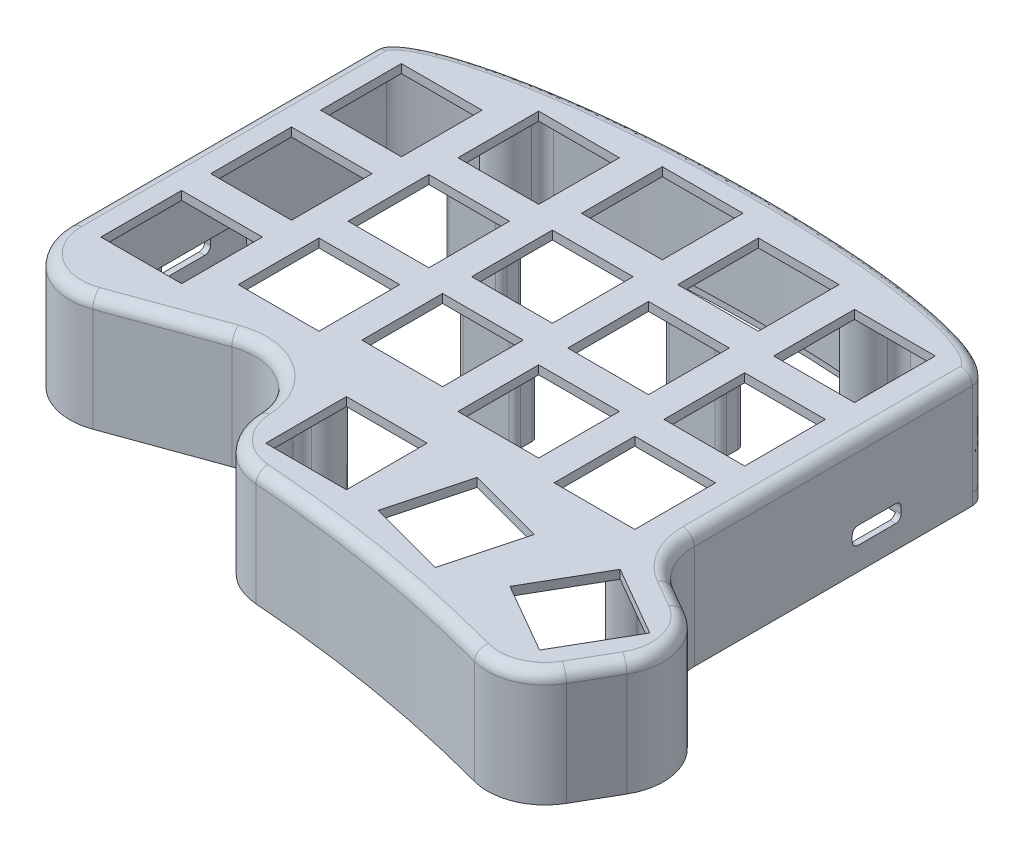
SolidWorks part; units mm, degrees
ref_plane "Front Plane" through (0, 0, 0) normal (0, 0, 1) x (1, 0, 0)
ref_plane "Top Plane" through (0, 0, 0) normal (0, 1, 0) x (1, 0, 0)
ref_plane "Right Plane" through (0, 0, 0) normal (1, 0, 0) x (0, 0, -1)
sketch "Sketch2" plane through (0, 0, 0) normal (0, 1, 0) x (1, 0, 0)
  line L0 (-52.3875, 73.6763) -> (-52.3875, 21.5763) construction
  line L1 (-60.1375, 66.6763) -> (-44.6375, 66.6763) construction
  line L2 (-52.1341, 56.3684) -> (-52.1341, 68.3684) construction
  line L4 (-102.7306, 67.1244) -> (-102.7306, 14.2787)
  line L5 (-1.5375, 69.6125) -> (-1.5375, 21.3832)
  line L13 (3.4635, 12.7224) -> (8.1059, 10.0427)
  line L14 (11.7677, -3.6171) -> (7.9274, -10.2704)
  line L15 (-89.3298, 4.8748) -> (-71.6235, 11.2781)
  line L24 (-90.4875, 66.5312) -> (-90.4875, 52.5312) construction
  line L26 (-71.4375, 71.2937) -> (-71.4375, 57.2937) construction
  line L28 (-52.3875, 73.6763) -> (-52.3875, 59.6763) construction
  line L30 (-33.3375, 71.2938) -> (-33.3375, 57.2938) construction
  line L32 (-14.2875, 68.9138) -> (-14.2875, 54.9138) construction
  line L34 (-90.4875, 47.4812) -> (-90.4875, 33.4812) construction
  line L36 (-71.4375, 52.2437) -> (-71.4375, 38.2437) construction
  line L38 (-52.3875, 54.6263) -> (-52.3875, 40.6263) construction
  line L40 (-33.3375, 52.2438) -> (-33.3375, 38.2438) construction
  line L42 (-14.2875, 49.8638) -> (-14.2875, 35.8638) construction
  line L44 (-14.2875, 30.8138) -> (-14.2875, 16.8138) construction
  line L46 (-33.3375, 33.1938) -> (-33.3375, 19.1937) construction
  line L48 (-71.4375, 33.1937) -> (-71.4375, 19.1937) construction
  line L51 (-90.4875, 28.4312) -> (-90.4875, 14.4312) construction
  line L52 (-52.3875, 35.5763) -> (-52.3875, 21.5763) construction
  line L54 (-45.2425, 11.7638) -> (-45.2425, -2.2362) construction
  line L56 (-83.4875, 52.5312) -> (-97.4875, 52.5312)
  line L57 (-83.4875, 52.5312) -> (-83.4875, 66.5312)
  line L58 (-83.4875, 66.5312) -> (-97.4875, 66.5312)
  line L59 (-97.4875, 52.5312) -> (-97.4875, 66.5312)
  line L60 (-83.4875, 52.5312) -> (-97.4875, 66.5312) construction
  line L61 (-83.4875, 66.5312) -> (-97.4875, 52.5312) construction
  line L63 (-64.4375, 57.2937) -> (-78.4375, 57.2937)
  line L64 (-64.4375, 57.2937) -> (-64.4375, 71.2937)
  line L65 (-64.4375, 71.2937) -> (-78.4375, 71.2937)
  line L66 (-78.4375, 57.2937) -> (-78.4375, 71.2937)
  line L67 (-64.4375, 57.2937) -> (-78.4375, 71.2937) construction
  line L68 (-64.4375, 71.2937) -> (-78.4375, 57.2937) construction
  line L71 (-45.3875, 59.6763) -> (-59.3875, 59.6763)
  line L72 (-45.3875, 59.6763) -> (-45.3875, 73.6763)
  line L73 (-45.3875, 73.6763) -> (-59.3875, 73.6763)
  line L74 (-59.3875, 59.6763) -> (-59.3875, 73.6763)
  line L75 (-45.3875, 59.6763) -> (-59.3875, 73.6763) construction
  line L76 (-45.3875, 73.6763) -> (-59.3875, 59.6763) construction
  line L78 (-26.3375, 57.2937) -> (-40.3375, 57.2937)
  line L79 (-26.3375, 57.2937) -> (-26.3375, 71.2937)
  line L80 (-26.3375, 71.2937) -> (-40.3375, 71.2937)
  line L81 (-40.3375, 57.2937) -> (-40.3375, 71.2937)
  line L82 (-26.3375, 57.2937) -> (-40.3375, 71.2937) construction
  line L83 (-26.3375, 71.2937) -> (-40.3375, 57.2937) construction
  line L85 (-7.2875, 54.9138) -> (-21.2875, 54.9138)
  line L86 (-7.2875, 54.9138) -> (-7.2875, 68.9138)
  line L87 (-7.2875, 68.9138) -> (-21.2875, 68.9138)
  line L88 (-21.2875, 54.9138) -> (-21.2875, 68.9138)
  line L89 (-7.2875, 54.9138) -> (-21.2875, 68.9138) construction
  line L90 (-7.2875, 68.9138) -> (-21.2875, 54.9138) construction
  line L92 (-7.2875, 35.8638) -> (-21.2875, 35.8638)
  line L93 (-7.2875, 35.8638) -> (-7.2875, 49.8638)
  line L94 (-7.2875, 49.8638) -> (-21.2875, 49.8638)
  line L95 (-21.2875, 35.8638) -> (-21.2875, 49.8638)
  line L96 (-7.2875, 35.8638) -> (-21.2875, 49.8638) construction
  line L97 (-7.2875, 49.8638) -> (-21.2875, 35.8638) construction
  line L99 (-26.3375, 38.2437) -> (-40.3375, 38.2437)
  line L100 (-26.3375, 38.2437) -> (-26.3375, 52.2437)
  line L101 (-26.3375, 52.2437) -> (-40.3375, 52.2437)
  line L102 (-40.3375, 38.2437) -> (-40.3375, 52.2437)
  line L103 (-26.3375, 38.2437) -> (-40.3375, 52.2437) construction
  line L104 (-26.3375, 52.2437) -> (-40.3375, 38.2437) construction
  line L106 (-45.3875, 40.6263) -> (-59.3875, 40.6263)
  line L107 (-45.3875, 40.6263) -> (-45.3875, 54.6263)
  line L108 (-45.3875, 54.6263) -> (-59.3875, 54.6263)
  line L109 (-59.3875, 40.6263) -> (-59.3875, 54.6263)
  line L110 (-45.3875, 40.6263) -> (-59.3875, 54.6263) construction
  line L111 (-45.3875, 54.6263) -> (-59.3875, 40.6263) construction
  line L113 (-64.4375, 38.2437) -> (-78.4375, 38.2437)
  line L114 (-64.4375, 38.2437) -> (-64.4375, 52.2437)
  line L115 (-64.4375, 52.2437) -> (-78.4375, 52.2437)
  line L116 (-78.4375, 38.2437) -> (-78.4375, 52.2437)
  line L117 (-64.4375, 38.2437) -> (-78.4375, 52.2437) construction
  line L118 (-64.4375, 52.2437) -> (-78.4375, 38.2437) construction
  line L120 (-83.4875, 33.4812) -> (-97.4875, 33.4812)
  line L121 (-83.4875, 33.4812) -> (-83.4875, 47.4812)
  line L122 (-83.4875, 47.4812) -> (-97.4875, 47.4812)
  line L123 (-97.4875, 33.4812) -> (-97.4875, 47.4812)
  line L124 (-83.4875, 33.4812) -> (-97.4875, 47.4812) construction
  line L125 (-83.4875, 47.4812) -> (-97.4875, 33.4812) construction
  line L127 (-83.4875, 14.4312) -> (-97.4875, 14.4312)
  line L128 (-83.4875, 14.4312) -> (-83.4875, 28.4312)
  line L129 (-83.4875, 28.4312) -> (-97.4875, 28.4312)
  line L130 (-97.4875, 14.4312) -> (-97.4875, 28.4312)
  line L131 (-83.4875, 14.4312) -> (-97.4875, 28.4312) construction
  line L132 (-83.4875, 28.4312) -> (-97.4875, 14.4312) construction
  line L134 (-64.4375, 19.1937) -> (-78.4375, 19.1937)
  line L135 (-64.4375, 19.1937) -> (-64.4375, 33.1937)
  line L136 (-64.4375, 33.1937) -> (-78.4375, 33.1937)
  line L137 (-78.4375, 19.1937) -> (-78.4375, 33.1937)
  line L138 (-64.4375, 19.1937) -> (-78.4375, 33.1937) construction
  line L139 (-64.4375, 33.1937) -> (-78.4375, 19.1937) construction
  line L141 (-26.3375, 19.1937) -> (-40.3375, 19.1937)
  line L142 (-26.3375, 19.1937) -> (-26.3375, 33.1937)
  line L143 (-26.3375, 33.1937) -> (-40.3375, 33.1937)
  line L144 (-40.3375, 19.1937) -> (-40.3375, 33.1937)
  line L145 (-26.3375, 19.1937) -> (-40.3375, 33.1937) construction
  line L146 (-26.3375, 33.1937) -> (-40.3375, 19.1937) construction
  line L148 (-7.2875, 16.8138) -> (-21.2875, 16.8138)
  line L149 (-7.2875, 16.8138) -> (-7.2875, 30.8138)
  line L150 (-7.2875, 30.8138) -> (-21.2875, 30.8138)
  line L151 (-21.2875, 16.8138) -> (-21.2875, 30.8138)
  line L152 (-7.2875, 16.8138) -> (-21.2875, 30.8138) construction
  line L153 (-7.2875, 30.8138) -> (-21.2875, 16.8138) construction
  line L155 (-38.2425, -2.2362) -> (-52.2425, -2.2362)
  line L156 (-38.2425, -2.2362) -> (-38.2425, 11.7638)
  line L157 (-38.2425, 11.7638) -> (-52.2425, 11.7638)
  line L158 (-52.2425, -2.2362) -> (-52.2425, 11.7638)
  line L159 (-38.2425, -2.2362) -> (-52.2425, 11.7638) construction
  line L160 (-38.2425, 11.7638) -> (-52.2425, -2.2362) construction
  line L161 (-60.1375, 28.5763) -> (-44.6375, 28.5763) construction
  line L163 (-21.9997, 9.1424) -> (-25.6253, -4.3799) construction
  line L166 (-45.3875, 21.5763) -> (-59.3875, 21.5763)
  line L167 (-45.3875, 21.5763) -> (-45.3875, 35.5763)
  line L168 (-45.3875, 35.5763) -> (-59.3875, 35.5763)
  line L169 (-59.3875, 21.5763) -> (-59.3875, 35.5763)
  line L170 (-45.3875, 21.5763) -> (-59.3875, 35.5763) construction
  line L171 (-45.3875, 35.5763) -> (-59.3875, 21.5763) construction
  line L173 (-18.8641, -6.1927) -> (-32.3865, -2.5672)
  line L174 (-18.8641, -6.1927) -> (-15.2385, 7.3297)
  line L175 (-15.2385, 7.3297) -> (-28.7609, 10.9552)
  line L176 (-32.3865, -2.5672) -> (-28.7609, 10.9552)
  line L177 (-18.8641, -6.1927) -> (-28.7609, 10.9552) construction
  line L178 (-15.2385, 7.3297) -> (-32.3865, -2.5672) construction
  line L180 (2.5633, -9.5619) -> (-9.5619, -2.5633)
  line L181 (2.5633, -9.5619) -> (9.5619, 2.5633)
  line L182 (9.5619, 2.5633) -> (-2.5633, 9.5619)
  line L183 (-9.5619, -2.5633) -> (-2.5633, 9.5619)
  line L184 (2.5633, -9.5619) -> (-2.5633, 9.5619) construction
  line L185 (9.5619, 2.5633) -> (-9.5619, -2.5633) construction
  arc A0 (-71.6235, 11.2781) -> (-58.2326, 2.3189) centre (-68.2227, 1.8741) cw
  arc A1 (-102.7306, 14.2787) -> (-89.3298, 4.8748) centre (-92.7306, 14.2787) ccw
  arc A2 (-1.5375, 21.3832) -> (3.4635, 12.7224) centre (8.4625, 21.3832) ccw
  arc A3 (8.1059, 10.0427) -> (11.7677, -3.6171) centre (3.1069, 1.3819) cw
  arc A4 (-48.9528, -7.211) -> (-3.3427, -14.9249) centre (-66.0135, -246.7815) cw
  arc A5 (7.9274, -10.2704) -> (-3.3427, -14.9249) centre (-0.7334, -5.2713) cw
  arc A6 (-58.2326, 2.3189) -> (-48.9528, -7.211) centre (-48.2425, 2.7638) ccw
  ellipse E0 centre (-52.1341, 56.3684) end of major axis (-1.5375, 57.6125) minor radius 10.3109 construction
  ellipse E1 centre (-52.1341, 68.3684) end of major axis (-1.5375, 69.6125) minor radius 10.3109 (-52.3875, 58.0487) -> (-52.1341, 58.0545) ccw
  ellipse E2 centre (-52.1341, 68.3684) end of major axis (-1.5375, 69.6125) minor radius 10.3109 (-1.5375, 69.6125) -> (-102.7306, 67.1244) ccw
  point P1 (-98.2375, 59.5312)
  point P3 (-6.5375, 61.9138)
  point P34 (-20.1589, -11.0222)
  point P39 (4.0192, -17.0414)
  point P86 (-71.4375, 64.2937)
  point P88 (-90.4875, 59.5312)
  point P96 (-52.3875, 66.6763)
  point P101 (-33.3375, 64.2938)
  point P106 (-14.2875, 61.9138)
  point P111 (-14.2875, 42.8638)
  point P116 (-33.3375, 45.2438)
  point P121 (-52.3875, 47.6263)
  point P126 (-71.4375, 45.2437)
  point P131 (-90.4875, 40.4812)
  point P136 (-90.4875, 21.4312)
  point P141 (-71.4375, 26.1937)
  point P146 (-33.3375, 26.1938)
  point P151 (-14.2875, 23.8138)
  point P156 (-45.2425, 4.7638)
  point P165 (-52.3875, 28.5763)
  point P170 (-23.8125, 2.3812)
  point P175 (0, 0)
  line B0 (3.8742, 6.7121) -> (-3.8742, -6.7121) construction
  line B1 (-6.0626, 3.4993) -> (6.0626, -3.4993) construction
  line B2 (9.0422, 2.8632) -> (9.4172, 3.5128)
  line B3 (9.4172, 3.5128) -> (-1.6687, 9.9115)
  line B4 (-1.6687, 9.9115) -> (-2.0436, 9.2619)
  line B5 (-2.0436, 9.2619) -> (-2.5633, 9.5619)
  line B6 (-2.5633, 9.5619) -> (-9.5619, -2.5633)
  line B7 (-9.5619, -2.5633) -> (-9.0422, -2.8632)
  line B8 (-9.0422, -2.8632) -> (-9.4172, -3.5128)
  line B9 (-9.4172, -3.5128) -> (1.6687, -9.9115)
  line B10 (1.6687, -9.9115) -> (2.0436, -9.2619)
  line B11 (2.0436, -9.2619) -> (2.5633, -9.5619)
  line B12 (2.5633, -9.5619) -> (9.5619, 2.5633)
  line B13 (9.5619, 2.5633) -> (9.0422, 2.8632)
  line B14 (-83.4875, 53.1312) -> (-82.7375, 53.1312)
  line B15 (-82.7375, 53.1312) -> (-82.7375, 65.9312)
  line B16 (-82.7375, 65.9312) -> (-83.4875, 65.9312)
  line B17 (-83.4875, 65.9312) -> (-83.4875, 66.5312)
  line B18 (-83.4875, 66.5312) -> (-97.4875, 66.5312)
  line B19 (-97.4875, 66.5312) -> (-97.4875, 65.9312)
  line B20 (-97.4875, 65.9312) -> (-98.2375, 65.9312)
  line B21 (-98.2375, 65.9312) -> (-98.2375, 53.1312)
  line B22 (-98.2375, 53.1312) -> (-97.4875, 53.1312)
  line B23 (-97.4875, 53.1312) -> (-97.4875, 52.5312)
  line B24 (-97.4875, 52.5312) -> (-83.4875, 52.5312)
  line B25 (-83.4875, 52.5312) -> (-83.4875, 53.1312)
  line B26 (-7.2875, 55.5138) -> (-6.5375, 55.5138)
  line B27 (-6.5375, 55.5138) -> (-6.5375, 68.3138)
  line B28 (-6.5375, 68.3138) -> (-7.2875, 68.3138)
  line B29 (-7.2875, 68.3138) -> (-7.2875, 68.9138)
  line B30 (-7.2875, 68.9138) -> (-21.2875, 68.9138)
  line B31 (-21.2875, 68.9138) -> (-21.2875, 68.3138)
  line B32 (-21.2875, 68.3138) -> (-22.0375, 68.3138)
  line B33 (-22.0375, 68.3138) -> (-22.0375, 55.5138)
  line B34 (-22.0375, 55.5138) -> (-21.2875, 55.5138)
  line B35 (-21.2875, 55.5138) -> (-21.2875, 54.9138)
  line B36 (-21.2875, 54.9138) -> (-7.2875, 54.9138)
  line B37 (-7.2875, 54.9138) -> (-7.2875, 55.5138)
  line B38 (-26.3375, 57.8938) -> (-25.5875, 57.8938)
  line B39 (-25.5875, 57.8938) -> (-25.5875, 70.6938)
  line B40 (-25.5875, 70.6938) -> (-26.3375, 70.6938)
  line B41 (-26.3375, 70.6938) -> (-26.3375, 71.2938)
  line B42 (-26.3375, 71.2938) -> (-40.3375, 71.2938)
  line B43 (-40.3375, 71.2938) -> (-40.3375, 70.6938)
  line B44 (-40.3375, 70.6938) -> (-41.0875, 70.6938)
  line B45 (-41.0875, 70.6938) -> (-41.0875, 57.8938)
  line B46 (-41.0875, 57.8938) -> (-40.3375, 57.8938)
  line B47 (-40.3375, 57.8938) -> (-40.3375, 57.2938)
  line B48 (-40.3375, 57.2938) -> (-26.3375, 57.2938)
  line B49 (-26.3375, 57.2938) -> (-26.3375, 57.8938)
  line B50 (-64.4375, 57.8937) -> (-63.6875, 57.8937)
  line B51 (-63.6875, 57.8937) -> (-63.6875, 70.6937)
  line B52 (-63.6875, 70.6937) -> (-64.4375, 70.6937)
  line B53 (-64.4375, 70.6937) -> (-64.4375, 71.2937)
  line B54 (-64.4375, 71.2937) -> (-78.4375, 71.2937)
  line B55 (-78.4375, 71.2937) -> (-78.4375, 70.6937)
  line B56 (-78.4375, 70.6937) -> (-79.1875, 70.6937)
  line B57 (-79.1875, 70.6937) -> (-79.1875, 57.8937)
  line B58 (-79.1875, 57.8937) -> (-78.4375, 57.8937)
  line B59 (-78.4375, 57.8937) -> (-78.4375, 57.2937)
  line B60 (-78.4375, 57.2937) -> (-64.4375, 57.2937)
  line B61 (-64.4375, 57.2937) -> (-64.4375, 57.8937)
  line B62 (-83.4875, 15.0312) -> (-82.7375, 15.0312)
  line B63 (-82.7375, 15.0312) -> (-82.7375, 27.8312)
  line B64 (-82.7375, 27.8312) -> (-83.4875, 27.8312)
  line B65 (-83.4875, 27.8312) -> (-83.4875, 28.4312)
  line B66 (-83.4875, 28.4312) -> (-97.4875, 28.4312)
  line B67 (-97.4875, 28.4312) -> (-97.4875, 27.8312)
  line B68 (-97.4875, 27.8312) -> (-98.2375, 27.8312)
  line B69 (-98.2375, 27.8312) -> (-98.2375, 15.0312)
  line B70 (-98.2375, 15.0312) -> (-97.4875, 15.0312)
  line B71 (-97.4875, 15.0312) -> (-97.4875, 14.4312)
  line B72 (-97.4875, 14.4312) -> (-83.4875, 14.4312)
  line B73 (-83.4875, 14.4312) -> (-83.4875, 15.0312)
  line B74 (-83.4875, 34.0812) -> (-82.7375, 34.0812)
  line B75 (-82.7375, 34.0812) -> (-82.7375, 46.8812)
  line B76 (-82.7375, 46.8812) -> (-83.4875, 46.8812)
  line B77 (-83.4875, 46.8812) -> (-83.4875, 47.4812)
  line B78 (-83.4875, 47.4812) -> (-97.4875, 47.4812)
  line B79 (-97.4875, 47.4812) -> (-97.4875, 46.8812)
  line B80 (-97.4875, 46.8812) -> (-98.2375, 46.8812)
  line B81 (-98.2375, 46.8812) -> (-98.2375, 34.0812)
  line B82 (-98.2375, 34.0812) -> (-97.4875, 34.0812)
  line B83 (-97.4875, 34.0812) -> (-97.4875, 33.4812)
  line B84 (-97.4875, 33.4812) -> (-83.4875, 33.4812)
  line B85 (-83.4875, 33.4812) -> (-83.4875, 34.0812)
  line B86 (-7.2875, 36.4638) -> (-6.5375, 36.4638)
  line B87 (-6.5375, 36.4638) -> (-6.5375, 49.2638)
  line B88 (-6.5375, 49.2638) -> (-7.2875, 49.2638)
  line B89 (-7.2875, 49.2638) -> (-7.2875, 49.8638)
  line B90 (-7.2875, 49.8638) -> (-21.2875, 49.8638)
  line B91 (-21.2875, 49.8638) -> (-21.2875, 49.2638)
  line B92 (-21.2875, 49.2638) -> (-22.0375, 49.2638)
  line B93 (-22.0375, 49.2638) -> (-22.0375, 36.4638)
  line B94 (-22.0375, 36.4638) -> (-21.2875, 36.4638)
  line B95 (-21.2875, 36.4638) -> (-21.2875, 35.8638)
  line B96 (-21.2875, 35.8638) -> (-7.2875, 35.8638)
  line B97 (-7.2875, 35.8638) -> (-7.2875, 36.4638)
  line B98 (-45.3875, 60.2763) -> (-44.6375, 60.2763)
  line B99 (-44.6375, 60.2763) -> (-44.6375, 73.0763)
  line B100 (-44.6375, 73.0763) -> (-45.3875, 73.0763)
  line B101 (-45.3875, 73.0763) -> (-45.3875, 73.6763)
  line B102 (-45.3875, 73.6763) -> (-59.3875, 73.6763)
  line B103 (-59.3875, 73.6763) -> (-59.3875, 73.0763)
  line B104 (-59.3875, 73.0763) -> (-60.1375, 73.0763)
  line B105 (-60.1375, 73.0763) -> (-60.1375, 60.2763)
  line B106 (-60.1375, 60.2763) -> (-59.3875, 60.2763)
  line B107 (-59.3875, 60.2763) -> (-59.3875, 59.6763)
  line B108 (-59.3875, 59.6763) -> (-45.3875, 59.6763)
  line B109 (-45.3875, 59.6763) -> (-45.3875, 60.2763)
  line B110 (-64.4375, 19.7937) -> (-63.6875, 19.7937)
  line B111 (-63.6875, 19.7937) -> (-63.6875, 32.5937)
  line B112 (-63.6875, 32.5937) -> (-64.4375, 32.5937)
  line B113 (-64.4375, 32.5937) -> (-64.4375, 33.1937)
  line B114 (-64.4375, 33.1937) -> (-78.4375, 33.1937)
  line B115 (-78.4375, 33.1937) -> (-78.4375, 32.5937)
  line B116 (-78.4375, 32.5937) -> (-79.1875, 32.5937)
  line B117 (-79.1875, 32.5937) -> (-79.1875, 19.7937)
  line B118 (-79.1875, 19.7937) -> (-78.4375, 19.7937)
  line B119 (-78.4375, 19.7937) -> (-78.4375, 19.1937)
  line B120 (-78.4375, 19.1937) -> (-64.4375, 19.1937)
  line B121 (-64.4375, 19.1937) -> (-64.4375, 19.7937)
  line B122 (-45.3875, 41.2263) -> (-44.6375, 41.2263)
  line B123 (-44.6375, 41.2263) -> (-44.6375, 54.0263)
  line B124 (-44.6375, 54.0263) -> (-45.3875, 54.0263)
  line B125 (-45.3875, 54.0263) -> (-45.3875, 54.6263)
  line B126 (-45.3875, 54.6263) -> (-59.3875, 54.6263)
  line B127 (-59.3875, 54.6263) -> (-59.3875, 54.0263)
  line B128 (-59.3875, 54.0263) -> (-60.1375, 54.0263)
  line B129 (-60.1375, 54.0263) -> (-60.1375, 41.2263)
  line B130 (-60.1375, 41.2263) -> (-59.3875, 41.2263)
  line B131 (-59.3875, 41.2263) -> (-59.3875, 40.6263)
  line B132 (-59.3875, 40.6263) -> (-45.3875, 40.6263)
  line B133 (-45.3875, 40.6263) -> (-45.3875, 41.2263)
  line B134 (-64.4375, 38.8437) -> (-63.6875, 38.8437)
  line B135 (-63.6875, 38.8437) -> (-63.6875, 51.6437)
  line B136 (-63.6875, 51.6437) -> (-64.4375, 51.6437)
  line B137 (-64.4375, 51.6437) -> (-64.4375, 52.2437)
  line B138 (-64.4375, 52.2437) -> (-78.4375, 52.2437)
  line B139 (-78.4375, 52.2437) -> (-78.4375, 51.6437)
  line B140 (-78.4375, 51.6437) -> (-79.1875, 51.6437)
  line B141 (-79.1875, 51.6437) -> (-79.1875, 38.8437)
  line B142 (-79.1875, 38.8437) -> (-78.4375, 38.8437)
  line B143 (-78.4375, 38.8437) -> (-78.4375, 38.2437)
  line B144 (-78.4375, 38.2437) -> (-64.4375, 38.2437)
  line B145 (-64.4375, 38.2437) -> (-64.4375, 38.8437)
  line B146 (-38.2425, -1.6362) -> (-37.4925, -1.6362)
  line B147 (-37.4925, -1.6362) -> (-37.4925, 11.1638)
  line B148 (-37.4925, 11.1638) -> (-38.2425, 11.1638)
  line B149 (-38.2425, 11.1638) -> (-38.2425, 11.7638)
  line B150 (-38.2425, 11.7638) -> (-52.2425, 11.7638)
  line B151 (-52.2425, 11.7638) -> (-52.2425, 11.1638)
  line B152 (-52.2425, 11.1638) -> (-52.9925, 11.1638)
  line B153 (-52.9925, 11.1638) -> (-52.9925, -1.6362)
  line B154 (-52.9925, -1.6362) -> (-52.2425, -1.6362)
  line B155 (-52.2425, -1.6362) -> (-52.2425, -2.2362)
  line B156 (-52.2425, -2.2362) -> (-38.2425, -2.2362)
  line B157 (-38.2425, -2.2362) -> (-38.2425, -1.6362)
  line B158 (-18.7087, -5.6132) -> (-17.9843, -5.8074)
  line B159 (-17.9843, -5.8074) -> (-14.6695, 6.5559)
  line B160 (-14.6695, 6.5559) -> (-15.3939, 6.7501)
  line B161 (-15.3939, 6.7501) -> (-15.2385, 7.3297)
  line B162 (-15.2385, 7.3297) -> (-28.7609, 10.9552)
  line B163 (-28.7609, 10.9552) -> (-28.9163, 10.3757)
  line B164 (-28.9163, 10.3757) -> (-29.6407, 10.5699)
  line B165 (-29.6407, 10.5699) -> (-32.9555, -1.7934)
  line B166 (-32.9555, -1.7934) -> (-32.2311, -1.9876)
  line B167 (-32.2311, -1.9876) -> (-32.3865, -2.5672)
  line B168 (-32.3865, -2.5672) -> (-18.8641, -6.1927)
  line B169 (-18.8641, -6.1927) -> (-18.7087, -5.6132)
  line B170 (-7.2875, 17.4138) -> (-6.5375, 17.4138)
  line B171 (-6.5375, 17.4138) -> (-6.5375, 30.2138)
  line B172 (-6.5375, 30.2138) -> (-7.2875, 30.2138)
  line B173 (-7.2875, 30.2138) -> (-7.2875, 30.8138)
  line B174 (-7.2875, 30.8138) -> (-21.2875, 30.8138)
  line B175 (-21.2875, 30.8138) -> (-21.2875, 30.2138)
  line B176 (-21.2875, 30.2138) -> (-22.0375, 30.2138)
  line B177 (-22.0375, 30.2138) -> (-22.0375, 17.4138)
  line B178 (-22.0375, 17.4138) -> (-21.2875, 17.4138)
  line B179 (-21.2875, 17.4138) -> (-21.2875, 16.8138)
  line B180 (-21.2875, 16.8138) -> (-7.2875, 16.8138)
  line B181 (-7.2875, 16.8138) -> (-7.2875, 17.4138)
  line B182 (-26.3375, 19.7938) -> (-25.5875, 19.7938)
  line B183 (-25.5875, 19.7938) -> (-25.5875, 32.5938)
  line B184 (-25.5875, 32.5938) -> (-26.3375, 32.5938)
  line B185 (-26.3375, 32.5938) -> (-26.3375, 33.1938)
  line B186 (-26.3375, 33.1938) -> (-40.3375, 33.1938)
  line B187 (-40.3375, 33.1938) -> (-40.3375, 32.5938)
  line B188 (-40.3375, 32.5938) -> (-41.0875, 32.5938)
  line B189 (-41.0875, 32.5938) -> (-41.0875, 19.7938)
  line B190 (-41.0875, 19.7938) -> (-40.3375, 19.7938)
  line B191 (-40.3375, 19.7938) -> (-40.3375, 19.1937)
  line B192 (-40.3375, 19.1937) -> (-26.3375, 19.1937)
  line B193 (-26.3375, 19.1937) -> (-26.3375, 19.7938)
  line B194 (-26.3375, 38.8438) -> (-25.5875, 38.8438)
  line B195 (-25.5875, 38.8438) -> (-25.5875, 51.6438)
  line B196 (-25.5875, 51.6438) -> (-26.3375, 51.6438)
  line B197 (-26.3375, 51.6438) -> (-26.3375, 52.2438)
  line B198 (-26.3375, 52.2438) -> (-40.3375, 52.2438)
  line B199 (-40.3375, 52.2438) -> (-40.3375, 51.6438)
  line B200 (-40.3375, 51.6438) -> (-41.0875, 51.6438)
  line B201 (-41.0875, 51.6438) -> (-41.0875, 38.8438)
  line B202 (-41.0875, 38.8438) -> (-40.3375, 38.8438)
  line B203 (-40.3375, 38.8438) -> (-40.3375, 38.2438)
  line B204 (-40.3375, 38.2438) -> (-26.3375, 38.2438)
  line B205 (-26.3375, 38.2438) -> (-26.3375, 38.8438)
  line B206 (-45.3875, 22.1763) -> (-44.6375, 22.1763)
  line B207 (-44.6375, 22.1763) -> (-44.6375, 34.9763)
  line B208 (-44.6375, 34.9763) -> (-45.3875, 34.9763)
  line B209 (-45.3875, 34.9763) -> (-45.3875, 35.5763)
  line B210 (-45.3875, 35.5763) -> (-59.3875, 35.5763)
  line B211 (-59.3875, 35.5763) -> (-59.3875, 34.9763)
  line B212 (-59.3875, 34.9763) -> (-60.1375, 34.9763)
  line B213 (-60.1375, 34.9763) -> (-60.1375, 22.1763)
  line B214 (-60.1375, 22.1763) -> (-59.3875, 22.1763)
  line B215 (-59.3875, 22.1763) -> (-59.3875, 21.5763)
  line B216 (-59.3875, 21.5763) -> (-45.3875, 21.5763)
  line B217 (-45.3875, 21.5763) -> (-45.3875, 22.1763)
  dimension "D9" = 10
  dimension "D10" = 10
  dimension "D14" = 10
  dimension "D1" = 5
  dimension "D2" = 4.4931
  dimension "D3" = 12
  dimension "D4" = 5
  dimension "D5" = 5
  dimension "D6" = 3
  dimension "D7" = 7
  dimension "D8" = 5
  dimension "D12" = 5
  dimension "D13" = 5
  dimension "D15" = 14
  dimension "D16" = 2
sketch_block_instance "Key_Layout-1"
sketch_block "Key_Layout"
extrude "Boss-Extrude1" add sketch "Sketch2" against normal blind 18 contours L5 E2 L4 A1 L15 A0 A6 A4 A5 L14 A3 L13 A2 B214 B213 B212 L169 L168 L167 B208 B207 B206 L166 B202 B201 B200 L102 L101 L100 B196 B195 B194 L99 B190 B189 B188 L144 L143 L142 | B21 B22 L59 B20 | B15 B16 L57 B14 | B57 B58 L66 B56 | B51 B52 L64 B50 | B105 B106 L74 B104 | B99 B100 L72 B98 | B45 B46 L81 B44 | B39 B40 L79 B38 | B33 B34 L88 B32 | B27 B28 L86 B26 | B87 B88 L93 B86 | B93 B94 L95 B92 | B195 B196 L100 B194 | B201 B202 L102 B200 | B123 B124 L107 B122 | B129 B130 L109 B128 | B135 B136 L114 B134 | B141 B142 L116 B140 | B75 B76 L121 B74 | B81 B82 L123 B80 | B69 B70 L130 B68 | B63 B64 L128 B62 | B117 B118 L137 B116 | B111 B112 L135 B110 | B213 B214 L169 B212 | B207 B208 L167 B206 | B189 B190 L144 B188 | B183 B184 L142 B182 | B177 B178 L151 B176 | B171 B172 L149 B170 | B3 B4 L182 B2 | B9 B10 L180 B8 | B159 B160 L174 B158 | B165 B166 L176 B164 | B147 B148 L156 B146 | B153 B154 L158 B152 region at (-52.3508, 0, -77.1848) region at (-83.1125, 0, -59.5312) region at (-97.8625, 0, -59.5312) region at (-64.0625, 0, -64.2937) region at (-78.8125, 0, -64.2937) region at (-45.0125, 0, -66.6763) region at (-59.7625, 0, -66.6763) region at (-25.9625, 0, -64.2938) region at (-40.7125, 0, -64.2938) region at (-6.9125, 0, -61.9138) region at (-21.6625, 0, -61.9138) region at (-6.9125, 0, -42.8638) region at (-21.6625, 0, -42.8638) region at (-25.9625, 0, -45.2438) region at (-40.7125, 0, -45.2438) region at (-45.0125, 0, -47.6263) region at (-59.7625, 0, -47.6263) region at (-64.0625, 0, -45.2437) region at (-78.8125, 0, -45.2437) region at (-83.1125, 0, -40.4812) region at (-97.8625, 0, -40.4812) region at (-83.1125, 0, -21.4312) region at (-97.8625, 0, -21.4312) region at (-64.0625, 0, -26.1937) region at (-78.8125, 0, -26.1937) region at (-25.9625, 0, -26.1938) region at (-40.7125, 0, -26.1938) region at (-6.9125, 0, -23.8138) region at (-21.6625, 0, -23.8138) region at (-37.8675, 0, -4.7638) region at (-52.6175, 0, -4.7638) region at (-45.0125, 0, -28.5763) region at (-59.7625, 0, -28.5763) region at (-16.6891, 0, -0.4714) region at (-30.9359, 0, -4.2911) region at (-3.6868, 0, 6.3874) region at (3.6868, 0, -6.3874)
sketch "Sketch3" plane through (0, 0, 0) normal (0, 1, 0) x (1, 0, 0)
  line L3 (-71.4375, 57.2937) -> (-71.4375, 52.2437) construction
  line L61 (-64.4375, 57.2937) -> (-78.4375, 57.2937) construction
  line L62 (-64.4375, 52.2437) -> (-78.4375, 52.2437) construction
  line L63 (-33.3375, 57.2937) -> (-33.3375, 52.2437) construction
  line L64 (-75.4375, 52.7687) -> (-67.4375, 52.7687)
  line L65 (-76.4375, 53.7687) -> (-76.4375, 55.7687)
  line L66 (-75.4375, 56.7687) -> (-67.4375, 56.7687)
  line L67 (-66.4375, 53.7687) -> (-66.4375, 55.7687)
  line L68 (-76.4375, 52.7687) -> (-66.4375, 56.7687) construction
  line L69 (-76.4375, 56.7687) -> (-66.4375, 52.7687) construction
  line L75 (-26.3375, 57.2937) -> (-40.3375, 57.2937) construction
  line L79 (-26.3375, 52.2437) -> (-40.3375, 52.2437) construction
  line L80 (-52.3875, 40.6263) -> (-52.3875, 35.5763) construction
  line L81 (-45.3875, 40.6263) -> (-59.3875, 40.6263) construction
  line L82 (-45.3875, 35.5763) -> (-59.3875, 35.5763) construction
  line L84 (-56.3875, 36.1013) -> (-48.3875, 36.1013)
  line L85 (-57.3875, 37.1013) -> (-57.3875, 39.1013)
  line L86 (-56.3875, 40.1013) -> (-48.3875, 40.1013)
  line L87 (-47.3875, 37.1013) -> (-47.3875, 39.1013)
  line L88 (-57.3875, 36.1013) -> (-47.3875, 40.1013) construction
  line L89 (-57.3875, 40.1013) -> (-47.3875, 36.1013) construction
  line L90 (-37.3375, 52.7687) -> (-29.3375, 52.7687)
  line L91 (-38.3375, 53.7687) -> (-38.3375, 55.7687)
  line L92 (-37.3375, 56.7687) -> (-29.3375, 56.7687)
  line L93 (-28.3375, 53.7687) -> (-28.3375, 55.7687)
  line L94 (-38.3375, 52.7687) -> (-28.3375, 56.7687) construction
  line L95 (-38.3375, 56.7687) -> (-28.3375, 52.7687) construction
  line L188 (-3.5375, 21.3832) -> (-3.5375, 69.5723)
  line L189 (7.1061, 8.3106) -> (2.4637, 10.9902)
  line L190 (6.1953, -9.2706) -> (10.0355, -2.6173)
  line L192 (-90.0099, 6.7556) -> (-72.3037, 13.1589)
  line L193 (-100.7306, 67.1646) -> (-100.7306, 14.2787)
  line L194 (-3.5375, 21.3832) -> (-3.5375, 69.5723)
  line L195 (7.1061, 8.3106) -> (2.4637, 10.9902)
  line L196 (6.1953, -9.2706) -> (10.0355, -2.6173)
  line L198 (-90.0099, 6.7556) -> (-72.3037, 13.1589)
  line L199 (-100.7306, 67.1646) -> (-100.7306, 14.2787)
  arc A14 (-28.3375, 53.7687) -> (-29.3375, 52.7687) centre (-29.3375, 53.7687) cw
  arc A15 (-28.3375, 55.7687) -> (-29.3375, 56.7687) centre (-29.3375, 55.7687) ccw
  arc A16 (-38.3375, 55.7687) -> (-37.3375, 56.7687) centre (-37.3375, 55.7687) cw
  arc A17 (-38.3375, 53.7687) -> (-37.3375, 52.7687) centre (-37.3375, 53.7687) ccw
  arc A18 (-47.3875, 37.1013) -> (-48.3875, 36.1013) centre (-48.3875, 37.1013) cw
  arc A19 (-48.3875, 40.1013) -> (-47.3875, 39.1013) centre (-48.3875, 39.1013) cw
  arc A20 (-57.3875, 37.1013) -> (-56.3875, 36.1013) centre (-56.3875, 37.1013) ccw
  arc A21 (-57.3875, 39.1013) -> (-56.3875, 40.1013) centre (-56.3875, 39.1013) cw
  arc A22 (-66.4375, 53.7687) -> (-67.4375, 52.7687) centre (-67.4375, 53.7687) cw
  arc A23 (-67.4375, 56.7687) -> (-66.4375, 55.7687) centre (-67.4375, 55.7687) cw
  arc A24 (-76.4375, 53.7687) -> (-75.4375, 52.7687) centre (-75.4375, 53.7687) ccw
  arc A25 (-76.4375, 55.7687) -> (-75.4375, 56.7687) centre (-75.4375, 55.7687) cw
  arc A97 (-3.5375, 21.3832) -> (2.4637, 10.9902) centre (8.4625, 21.3832) ccw
  arc A98 (10.0355, -2.6173) -> (7.1061, 8.3106) centre (3.1069, 1.3819) ccw
  arc A99 (-2.8209, -12.9942) -> (6.1953, -9.2706) centre (-0.7334, -5.2713) ccw
  arc A100 (-2.8209, -12.9942) -> (-48.8107, -5.216) centre (-66.0135, -246.7815) ccw
  arc A101 (-56.2346, 2.4079) -> (-48.8107, -5.216) centre (-48.2425, 2.7638) ccw
  arc A102 (-56.2346, 2.4079) -> (-72.3037, 13.1589) centre (-68.2227, 1.8741) ccw
  arc A103 (-100.7306, 14.2787) -> (-90.0099, 6.7556) centre (-92.7306, 14.2787) ccw
  arc A104 (-3.5375, 21.3832) -> (2.4637, 10.9902) centre (8.4625, 21.3832) ccw
  arc A105 (10.0355, -2.6173) -> (7.1061, 8.3106) centre (3.1069, 1.3819) ccw
  arc A106 (-2.8209, -12.9942) -> (6.1953, -9.2706) centre (-0.7334, -5.2713) ccw
  arc A107 (-2.8209, -12.9942) -> (-48.8107, -5.216) centre (-66.0135, -246.7815) ccw
  arc A108 (-56.2346, 2.4079) -> (-48.8107, -5.216) centre (-48.2425, 2.7638) ccw
  arc A109 (-56.2346, 2.4079) -> (-72.3037, 13.1589) centre (-68.2227, 1.8741) ccw
  arc A110 (-100.7306, 14.2787) -> (-90.0099, 6.7556) centre (-92.7306, 14.2787) ccw
  spline S0 degree 3 poles (-1951.4676, -379.6605) (-4.4919, 63.5376) (-2.7302, 67.8112) (-3.582, 69.6988) (-3.5979, 69.7282) (-3.6492, 69.814) (-3.6882, 69.8682) (-3.8132, 70.0256) (-3.9052, 70.1212) (-4.1943, 70.393) (-4.4056, 70.5549) (-5.0614, 71.0066) (-5.5225, 71.259) (-6.4661, 71.7207) (-6.9495, 71.9279) (-7.931, 72.3125) (-8.4288, 72.4893) (-9.926, 72.9834) (-10.934, 73.2666) (-12.9619, 73.7775) (-13.982, 74.0045) (-17.0551, 74.6246) (-19.1211, 74.9581) (-22.2363, 75.3822) (-23.2777, 75.5104) (-25.358, 75.7437) (-26.3979, 75.8489) (-31.5962, 76.3247) (-35.7511, 76.55) (-44.0555, 76.778) (-52.3546, 76.7795) (-60.6437, 76.3692) (-68.9275, 75.7323) (-73.0667, 75.3025) (-79.27, 74.4243) (-81.3396, 74.0917) (-85.4619, 73.3214) (-87.5141, 72.8851) (-90.5626, 72.1105) (-91.5733, 71.8321) (-93.5794, 71.2182) (-94.5733, 70.8839) (-96.0407, 70.3155) (-96.5252, 70.115) (-97.4808, 69.6829) (-97.9521, 69.4516) (-98.869, 68.9422) (-99.3167, 68.665) (-99.9393, 68.1841) (-100.1392, 68.0129) (-100.41, 67.7271) (-100.4955, 67.6271) (-100.6082, 67.4654) (-100.6431, 67.4097) (-100.6877, 67.3218) (-100.7012, 67.2919) (-101.2824, 65.656) (-101.6035, 60.6186) (1897.5604, 127.7173) knots -0.058166 -0.058166 -0.058166 -0.058166 0.000977 0.000977 0.001953 0.001953 0.003906 0.003906 0.007812 0.007812 0.015625 0.015625 0.03125 0.03125 0.046875 0.046875 0.0625 0.0625 0.09375 0.09375 0.125 0.125 0.1875 0.1875 0.21875 0.21875 0.25 0.25 0.375 0.375 0.5 0.625 0.625 0.75 0.75 0.8125 0.8125 0.875 0.875 0.90625 0.90625 0.9375 0.9375 0.953125 0.953125 0.96875 0.96875 0.984375 0.984375 0.992188 0.992188 0.996094 0.996094 0.998047 0.998047 0.999023 0.999023 1.049594 1.049594 1.049594 1.049594 only from (-3.5375, 69.5723) to (-100.7306, 67.1646)
  spline S1 degree 3 poles (-3.5375, 69.5723) (-3.5412, 69.6062) (-3.5543, 69.6375) (-3.582, 69.6988) (-3.5979, 69.7282) (-3.6492, 69.814) (-3.6882, 69.8682) (-3.8132, 70.0256) (-3.9052, 70.1212) (-4.1943, 70.393) (-4.4056, 70.5549) (-5.0614, 71.0066) (-5.5225, 71.259) (-6.4661, 71.7207) (-6.9495, 71.9279) (-7.931, 72.3125) (-8.4288, 72.4893) (-9.926, 72.9834) (-10.934, 73.2666) (-12.9619, 73.7775) (-13.982, 74.0045) (-17.0551, 74.6246) (-19.1211, 74.9581) (-22.2363, 75.3822) (-23.2777, 75.5104) (-25.358, 75.7437) (-26.3979, 75.8489) (-31.5962, 76.3247) (-35.7511, 76.55) (-44.0555, 76.778) (-52.3546, 76.7795) (-60.6437, 76.3692) (-68.9275, 75.7323) (-73.0667, 75.3025) (-79.27, 74.4243) (-81.3396, 74.0917) (-85.4619, 73.3214) (-87.5141, 72.8851) (-90.5626, 72.1105) (-91.5733, 71.8321) (-93.5794, 71.2182) (-94.5733, 70.8839) (-96.0407, 70.3155) (-96.5252, 70.115) (-97.4808, 69.6829) (-97.9521, 69.4516) (-98.869, 68.9422) (-99.3167, 68.665) (-99.9393, 68.1841) (-100.1392, 68.0129) (-100.41, 67.7271) (-100.4955, 67.6271) (-100.6082, 67.4654) (-100.6431, 67.4097) (-100.6877, 67.3218) (-100.7012, 67.2919) (-100.7233, 67.2299) (-100.7342, 67.1976) (-100.7306, 67.1646) knots 0 0 0 0 0.000977 0.000977 0.001953 0.001953 0.003906 0.003906 0.007812 0.007812 0.015625 0.015625 0.03125 0.03125 0.046875 0.046875 0.0625 0.0625 0.09375 0.09375 0.125 0.125 0.1875 0.1875 0.21875 0.21875 0.25 0.25 0.375 0.375 0.5 0.625 0.625 0.75 0.75 0.8125 0.8125 0.875 0.875 0.90625 0.90625 0.9375 0.9375 0.953125 0.953125 0.96875 0.96875 0.984375 0.984375 0.992188 0.992188 0.996094 0.996094 0.998047 0.998047 0.999023 0.999023 1 1 1 1
  point P6 (-71.4375, 54.7687)
  point P23 (-52.3875, 38.1013)
  point P28 (-33.3375, 54.7687)
  dimension "D8" = 1
  dimension "D2" = 10
  dimension "D3" = 4
  dimension "D4" = 10
  dimension "D6" = 10
  dimension "D7" = 4
  dimension "D1" = 2
extrude "Cut-Extrude1" cut sketch "Sketch3" along normal offset from surface (16.5 mm away) 1.5 from surface contours L65 A25 L66 A23 L67 A22 L64 A24 L85 A21 L86 A19 L87 A18 L84 A20 A17 L91 A16 L92 A15 L93 A14 L90 region at (-46.6992, 0, -35.3693) up to face at (-52.3875, 0, -28.5763) starting at face at (-52.3875, -18, -28.5763)
fillet "Fillet2" radius 2 13 edges at (-1.5375, 0, -45.4978) (-0.1975, 0, -16.3827) (5.7847, 0, -11.3825) (12.7659, 0, -3.9712) (9.8476, 0, 6.9437) (3.0839, 0, 14.5141) (-25.9616, 0, 9.9673) (-55.407, 0, 4.2126) (-62.662, 0, -10.1855) (-80.4766, 0, -8.0764) (-98.4748, 0, -6.0931) (-102.7306, 0, -40.7016) (-52.3875, 0, -78.6763)
sketch "Sketch5" plane through (0, 0, 0) normal (0, 1, 0) x (1, 0, 0)
  line L0 (-90.0099, 6.7556) -> (-72.3037, 13.1589) construction
  line L6 (-3.5375, 21.3832) -> (-3.5375, 69.5723) construction
  line L7 (-100.7306, 67.1646) -> (-100.7306, 14.2787) construction
  line L44 (-3.5375, 21.3832) -> (-3.5375, 69.5723)
  line L45 (7.1061, 8.3106) -> (2.4637, 10.9902)
  line L46 (6.1953, -9.2706) -> (10.0355, -2.6173)
  line L47 (-90.0099, 6.7556) -> (-72.3037, 13.1589)
  line L48 (-100.7306, 67.1646) -> (-100.7306, 14.2787)
  line L49 (-3.5375, 21.3832) -> (-3.5375, 69.5723)
  line L50 (7.1061, 8.3106) -> (2.4637, 10.9902)
  line L51 (6.1953, -9.2706) -> (10.0355, -2.6173)
  line L52 (-90.0099, 6.7556) -> (-72.3037, 13.1589)
  line L53 (-100.7306, 67.1646) -> (-100.7306, 14.2787)
  circle A9 centre (-22.5375, 72.1398) radius 1.75
  circle A10 centre (-22.5375, 72.1398) radius 3.25
  circle A11 centre (-83.2306, 70.4313) radius 1.75
  circle A12 centre (-83.2306, 70.4313) radius 3.25
  circle A13 centre (-58.7306, 13.8099) radius 1.75
  circle A14 centre (-58.7306, 13.8099) radius 3.25
  circle A15 centre (-4.7375, 13.7463) radius 1.75
  circle A54 centre (-4.7375, 13.7463) radius 3.25
  circle A55 centre (-17.5982, 72.9165) radius 1.75
  circle A56 centre (-27.1128, 74.1563) radius 1.75
  circle A57 centre (-78.7827, 72.7151) radius 1.75
  circle A58 centre (-88.2088, 70.8973) radius 1.75
  arc A59 (-3.5375, 21.3832) -> (2.4637, 10.9902) centre (8.4625, 21.3832) ccw construction
  arc A60 (-56.2346, 2.4079) -> (-72.3037, 13.1589) centre (-68.2227, 1.8741) ccw construction
  circle A61 centre (-9.5375, -7.9406) radius 1.75
  circle A62 centre (-9.5375, -7.9406) radius 3.25
  circle A63 centre (-93.2306, 9.5551) radius 1.75
  circle A64 centre (-93.2306, 9.5551) radius 3.25
  arc A65 (-2.8209, -12.9942) -> (-48.8107, -5.216) centre (-66.0135, -246.7815) ccw construction
  arc A66 (-100.7306, 14.2787) -> (-90.0099, 6.7556) centre (-92.7306, 14.2787) ccw construction
  circle A67 centre (-0.5564, 11.0043) radius 1.75
  circle A68 centre (-5.0306, 18.7377) radius 1.75
  circle A69 centre (-5.2661, -10.5396) radius 1.75
  circle A70 centre (-14.5206, -8.3513) radius 1.75
  circle A71 centre (-63.6249, 14.8326) radius 1.75
  circle A72 centre (-56.6322, 9.2716) radius 1.75
  circle A73 centre (-88.2395, 9.2567) radius 1.75
  circle A74 centre (-98.0284, 10.9627) radius 1.75
  arc A129 (-3.5375, 21.3832) -> (2.4637, 10.9902) centre (8.4625, 21.3832) ccw
  arc A130 (10.0355, -2.6173) -> (7.1061, 8.3106) centre (3.1069, 1.3819) ccw
  arc A131 (-2.8209, -12.9942) -> (6.1953, -9.2706) centre (-0.7334, -5.2713) ccw
  arc A132 (-2.8209, -12.9942) -> (-48.8107, -5.216) centre (-66.0135, -246.7815) ccw
  arc A133 (-56.2346, 2.4079) -> (-48.8107, -5.216) centre (-48.2425, 2.7638) ccw
  arc A134 (-56.2346, 2.4079) -> (-72.3037, 13.1589) centre (-68.2227, 1.8741) ccw
  arc A135 (-100.7306, 14.2787) -> (-90.0099, 6.7556) centre (-92.7306, 14.2787) ccw
  arc A136 (-3.5375, 21.3832) -> (2.4637, 10.9902) centre (8.4625, 21.3832) ccw
  arc A137 (10.0355, -2.6173) -> (7.1061, 8.3106) centre (3.1069, 1.3819) ccw
  arc A138 (-2.8209, -12.9942) -> (6.1953, -9.2706) centre (-0.7334, -5.2713) ccw
  arc A139 (-2.8209, -12.9942) -> (-48.8107, -5.216) centre (-66.0135, -246.7815) ccw
  arc A140 (-56.2346, 2.4079) -> (-48.8107, -5.216) centre (-48.2425, 2.7638) ccw
  arc A141 (-56.2346, 2.4079) -> (-72.3037, 13.1589) centre (-68.2227, 1.8741) ccw
  arc A142 (-100.7306, 14.2787) -> (-90.0099, 6.7556) centre (-92.7306, 14.2787) ccw
  spline S0 degree 3 poles (-3.5375, 69.5723) (-3.5412, 69.6062) (-3.5543, 69.6375) (-3.582, 69.6988) (-3.5979, 69.7282) (-3.6492, 69.814) (-3.6882, 69.8682) (-3.8132, 70.0256) (-3.9052, 70.1212) (-4.1943, 70.393) (-4.4056, 70.5549) (-5.0614, 71.0066) (-5.5225, 71.259) (-6.4661, 71.7207) (-6.9495, 71.9279) (-7.931, 72.3125) (-8.4288, 72.4893) (-9.926, 72.9834) (-10.934, 73.2666) (-12.9619, 73.7775) (-13.982, 74.0045) (-17.0551, 74.6246) (-19.1211, 74.9581) (-22.2363, 75.3822) (-23.2777, 75.5104) (-25.358, 75.7437) (-26.3979, 75.8489) (-31.5962, 76.3247) (-35.7511, 76.55) (-44.0555, 76.778) (-52.3546, 76.7795) (-60.6437, 76.3692) (-68.9275, 75.7323) (-73.0667, 75.3025) (-79.27, 74.4243) (-81.3396, 74.0917) (-85.4619, 73.3214) (-87.5141, 72.8851) (-90.5626, 72.1105) (-91.5733, 71.8321) (-93.5794, 71.2182) (-94.5733, 70.8839) (-96.0407, 70.3155) (-96.5252, 70.115) (-97.4808, 69.6829) (-97.9521, 69.4516) (-98.869, 68.9422) (-99.3167, 68.665) (-99.9393, 68.1841) (-100.1392, 68.0129) (-100.41, 67.7271) (-100.4955, 67.6271) (-100.6082, 67.4654) (-100.6431, 67.4097) (-100.6877, 67.3218) (-100.7012, 67.2919) (-100.7233, 67.2299) (-100.7342, 67.1976) (-100.7306, 67.1646) knots 0 0 0 0 0.000977 0.000977 0.001953 0.001953 0.003906 0.003906 0.007812 0.007812 0.015625 0.015625 0.03125 0.03125 0.046875 0.046875 0.0625 0.0625 0.09375 0.09375 0.125 0.125 0.1875 0.1875 0.21875 0.21875 0.25 0.25 0.375 0.375 0.5 0.625 0.625 0.75 0.75 0.8125 0.8125 0.875 0.875 0.90625 0.90625 0.9375 0.9375 0.953125 0.953125 0.96875 0.96875 0.984375 0.984375 0.992188 0.992188 0.996094 0.996094 0.998047 0.998047 0.999023 0.999023 1 1 1 1 construction
  spline S15 degree 3 poles (-4876.0099, -1043.6391) (-6.0847, 60.1713) (-2.4304, 67.147) (-3.582, 69.6988) (-3.5979, 69.7282) (-3.6492, 69.814) (-3.6882, 69.8682) (-3.8132, 70.0256) (-3.9052, 70.1212) (-4.1943, 70.393) (-4.4056, 70.5549) (-5.0614, 71.0066) (-5.5225, 71.259) (-6.4661, 71.7207) (-6.9495, 71.9279) (-7.931, 72.3125) (-8.4288, 72.4893) (-9.926, 72.9834) (-10.934, 73.2666) (-12.9619, 73.7775) (-13.982, 74.0045) (-17.0551, 74.6246) (-19.1211, 74.9581) (-22.2363, 75.3822) (-23.2777, 75.5104) (-25.358, 75.7437) (-26.3979, 75.8489) (-31.5962, 76.3247) (-35.7511, 76.55) (-44.0555, 76.778) (-52.3546, 76.7795) (-60.6437, 76.3692) (-68.9275, 75.7323) (-73.0667, 75.3025) (-79.27, 74.4243) (-81.3396, 74.0917) (-85.4619, 73.3214) (-87.5141, 72.8851) (-90.5626, 72.1105) (-91.5733, 71.8321) (-93.5794, 71.2182) (-94.5733, 70.8839) (-96.0407, 70.3155) (-96.5252, 70.115) (-97.4808, 69.6829) (-97.9521, 69.4516) (-98.869, 68.9422) (-99.3167, 68.665) (-99.9393, 68.1841) (-100.1392, 68.0129) (-100.41, 67.7271) (-100.4955, 67.6271) (-100.6082, 67.4654) (-100.6431, 67.4097) (-100.6877, 67.3218) (-100.7012, 67.2919) (-101.4859, 65.0831) (-101.8009, 56.5858) (4893.0241, 230.561) knots -0.07932 -0.07932 -0.07932 -0.07932 0.000977 0.000977 0.001953 0.001953 0.003906 0.003906 0.007812 0.007812 0.015625 0.015625 0.03125 0.03125 0.046875 0.046875 0.0625 0.0625 0.09375 0.09375 0.125 0.125 0.1875 0.1875 0.21875 0.21875 0.25 0.25 0.375 0.375 0.5 0.625 0.625 0.75 0.75 0.8125 0.8125 0.875 0.875 0.90625 0.90625 0.9375 0.9375 0.953125 0.953125 0.96875 0.96875 0.984375 0.984375 0.992188 0.992188 0.996094 0.996094 0.998047 0.998047 0.999023 0.999023 1.067642 1.067642 1.067642 1.067642 only from (-3.5375, 69.5723) to (-100.7306, 67.1646)
  spline S16 degree 3 poles (-3.5375, 69.5723) (-3.5412, 69.6062) (-3.5543, 69.6375) (-3.582, 69.6988) (-3.5979, 69.7282) (-3.6492, 69.814) (-3.6882, 69.8682) (-3.8132, 70.0256) (-3.9052, 70.1212) (-4.1943, 70.393) (-4.4056, 70.5549) (-5.0614, 71.0066) (-5.5225, 71.259) (-6.4661, 71.7207) (-6.9495, 71.9279) (-7.931, 72.3125) (-8.4288, 72.4893) (-9.926, 72.9834) (-10.934, 73.2666) (-12.9619, 73.7775) (-13.982, 74.0045) (-17.0551, 74.6246) (-19.1211, 74.9581) (-22.2363, 75.3822) (-23.2777, 75.5104) (-25.358, 75.7437) (-26.3979, 75.8489) (-31.5962, 76.3247) (-35.7511, 76.55) (-44.0555, 76.778) (-52.3546, 76.7795) (-60.6437, 76.3692) (-68.9275, 75.7323) (-73.0667, 75.3025) (-79.27, 74.4243) (-81.3396, 74.0917) (-85.4619, 73.3214) (-87.5141, 72.8851) (-90.5626, 72.1105) (-91.5733, 71.8321) (-93.5794, 71.2182) (-94.5733, 70.8839) (-96.0407, 70.3155) (-96.5252, 70.115) (-97.4808, 69.6829) (-97.9521, 69.4516) (-98.869, 68.9422) (-99.3167, 68.665) (-99.9393, 68.1841) (-100.1392, 68.0129) (-100.41, 67.7271) (-100.4955, 67.6271) (-100.6082, 67.4654) (-100.6431, 67.4097) (-100.6877, 67.3218) (-100.7012, 67.2919) (-100.7233, 67.2299) (-100.7342, 67.1976) (-100.7306, 67.1646) knots 0 0 0 0 0.000977 0.000977 0.001953 0.001953 0.003906 0.003906 0.007812 0.007812 0.015625 0.015625 0.03125 0.03125 0.046875 0.046875 0.0625 0.0625 0.09375 0.09375 0.125 0.125 0.1875 0.1875 0.21875 0.21875 0.25 0.25 0.375 0.375 0.5 0.625 0.625 0.75 0.75 0.8125 0.8125 0.875 0.875 0.90625 0.90625 0.9375 0.9375 0.953125 0.953125 0.96875 0.96875 0.984375 0.984375 0.992188 0.992188 0.996094 0.996094 0.998047 0.998047 0.999023 0.999023 1 1 1 1
  dimension "D2" = 3.5
  dimension "D5" = 3.5
  dimension "D8" = 3.5
  dimension "D10" = 3.5
  dimension "D12" = 3.5
  dimension "D13" = 3.5
  dimension "D14" = 3.5
  dimension "D15" = 3.5
  dimension "D16" = 3.5
  dimension "D18" = 3.5
  dimension "D20" = 3.5
  dimension "D21" = 3.5
  dimension "D22" = 3.5
  dimension "D23" = 3.5
  dimension "D24" = 3.5
  dimension "D25" = 3.5
  dimension "D26" = 3.5
  dimension "D27" = 3.5
  dimension "D3" = 1.5
  dimension "D6" = 1.5
  dimension "D9" = 1.5
  dimension "D11" = 1.5
  dimension "D4" = 19
  dimension "D7" = 17.5
  dimension "D17" = 1.5
  dimension "D19" = 1.5
  dimension "D28" = 1.2
  dimension "D29" = 6
  dimension "D30" = 42
  dimension "D31" = 7.5
  dimension "D32" = 0
extrude "Boss-Extrude2" add sketch "Sketch5" against normal up to surface (18 mm away) from surface contours A10 A9 | A55 S16 A10 | A10 S16 A56 | A12 A11 | A12 S16 A58 | A57 S16 A12 | A64 A63 | A74 A142 A64 | A64 A142 L52 A73 | A14 A13 | A141 A14 A71 | A141 A72 A14 | A62 A61 | A139 A62 A70 | A139 A69 A62 | A54 A15 | A136 A68 A54 | A136 A54 A67 region at (-3.2638, 0, -17.1769) region at (-3.2406, 0, -16.527) region at (-1.0288, 0, -13.3139) region at (-86.3666, 0, -72.5776) region at (-19.5415, 0, -74.4761) region at (-85.5672, 0, -72.5559) region at (-81.1159, 0, -73.5848) region at (-19.389, 0, -72.3858) region at (-24.8358, 0, -75.1616) region at (-96.9476, 0, -8.3311) region at (-92.7815, 0, -12.6811) region at (-90.1917, 0, -7.3109) region at (-7.6397, 0, 11.2191) region at (-62.3404, 0, -12.8558) region at (-8.3194, 0, 10.8543) region at (-12.7027, 0, 10.0219) region at (-58.4059, 0, -16.9513) region at (-58.8474, 0, -10.078) up to face at (-33.3375, -18, -54.7687) starting at face at (-90.4875, -1.5, -59.5312)
sketch "Sketch6" plane through (0, 0, 0) normal (0, 1, 0) x (1, 0, 0)
  line L12 (-2.5375, 21.3832) -> (-2.5375, 69.5982)
  line L13 (7.606, 9.1767) -> (2.9636, 11.8563)
  line L14 (7.0614, -9.7705) -> (10.9016, -3.1172)
  line L16 (-89.6698, 5.8152) -> (-71.9636, 12.2185)
  line L17 (-101.7306, 67.1387) -> (-101.7306, 14.2787)
  line L18 (-2.5375, 21.3832) -> (-2.5375, 69.5982)
  line L19 (7.606, 9.1767) -> (2.9636, 11.8563)
  line L20 (7.0614, -9.7705) -> (10.9016, -3.1172)
  line L22 (-89.6698, 5.8152) -> (-71.9636, 12.2185)
  line L23 (-101.7306, 67.1387) -> (-101.7306, 14.2787)
  line L24 (-1.5375, 21.3832) -> (-1.5375, 69.6125)
  line L25 (8.1059, 10.0427) -> (3.4635, 12.7224)
  line L26 (7.9274, -10.2704) -> (11.7677, -3.6171)
  line L28 (-89.3298, 4.8748) -> (-71.6235, 11.2781)
  line L29 (-102.7306, 67.1244) -> (-102.7306, 14.2787)
  line L30 (-1.5375, 21.3832) -> (-1.5375, 69.6125)
  line L31 (8.1059, 10.0427) -> (3.4635, 12.7224)
  line L32 (7.9274, -10.2704) -> (11.7677, -3.6171)
  line L34 (-89.3298, 4.8748) -> (-71.6235, 11.2781)
  line L35 (-102.7306, 67.1244) -> (-102.7306, 14.2787)
  arc A14 (-2.5375, 21.3832) -> (2.9636, 11.8563) centre (8.4625, 21.3832) ccw
  arc A15 (10.9016, -3.1172) -> (7.606, 9.1767) centre (3.1069, 1.3819) ccw
  arc A16 (-3.0818, -13.9595) -> (7.0614, -9.7705) centre (-0.7334, -5.2713) ccw
  arc A17 (-3.0818, -13.9595) -> (-48.8818, -6.2135) centre (-66.0135, -246.7815) ccw
  arc A18 (-57.2336, 2.3634) -> (-48.8818, -6.2135) centre (-48.2425, 2.7638) ccw
  arc A19 (-57.2336, 2.3634) -> (-71.9636, 12.2185) centre (-68.2227, 1.8741) ccw
  arc A20 (-101.7306, 14.2787) -> (-89.6698, 5.8152) centre (-92.7306, 14.2787) ccw
  arc A21 (-2.5375, 21.3832) -> (2.9636, 11.8563) centre (8.4625, 21.3832) ccw
  arc A22 (10.9016, -3.1172) -> (7.606, 9.1767) centre (3.1069, 1.3819) ccw
  arc A23 (-3.0818, -13.9595) -> (7.0614, -9.7705) centre (-0.7334, -5.2713) ccw
  arc A24 (-3.0818, -13.9595) -> (-48.8818, -6.2135) centre (-66.0135, -246.7815) ccw
  arc A25 (-57.2336, 2.3634) -> (-48.8818, -6.2135) centre (-48.2425, 2.7638) ccw
  arc A26 (-57.2336, 2.3634) -> (-71.9636, 12.2185) centre (-68.2227, 1.8741) ccw
  arc A27 (-101.7306, 14.2787) -> (-89.6698, 5.8152) centre (-92.7306, 14.2787) ccw
  arc A28 (-1.5375, 21.3832) -> (3.4635, 12.7224) centre (8.4625, 21.3832) ccw
  arc A29 (11.7677, -3.6171) -> (8.1059, 10.0427) centre (3.1069, 1.3819) ccw
  arc A30 (-3.3427, -14.9249) -> (7.9274, -10.2704) centre (-0.7334, -5.2713) ccw
  arc A31 (-3.3427, -14.9249) -> (-48.9528, -7.211) centre (-66.0135, -246.7815) ccw
  arc A32 (-58.2326, 2.3189) -> (-48.9528, -7.211) centre (-48.2425, 2.7638) ccw
  arc A33 (-58.2326, 2.3189) -> (-71.6235, 11.2781) centre (-68.2227, 1.8741) ccw
  arc A34 (-102.7306, 14.2787) -> (-89.3298, 4.8748) centre (-92.7306, 14.2787) ccw
  arc A35 (-1.5375, 21.3832) -> (3.4635, 12.7224) centre (8.4625, 21.3832) ccw
  arc A36 (11.7677, -3.6171) -> (8.1059, 10.0427) centre (3.1069, 1.3819) ccw
  arc A37 (-3.3427, -14.9249) -> (7.9274, -10.2704) centre (-0.7334, -5.2713) ccw
  arc A38 (-3.3427, -14.9249) -> (-48.9528, -7.211) centre (-66.0135, -246.7815) ccw
  arc A39 (-58.2326, 2.3189) -> (-48.9528, -7.211) centre (-48.2425, 2.7638) ccw
  arc A40 (-58.2326, 2.3189) -> (-71.6235, 11.2781) centre (-68.2227, 1.8741) ccw
  arc A41 (-102.7306, 14.2787) -> (-89.3298, 4.8748) centre (-92.7306, 14.2787) ccw
  ellipse E2 centre (-52.1341, 68.3684) end of major axis (-102.7306, 67.1244) minor radius 10.3109 (-1.5375, 69.6125) -> (-102.7306, 67.1244) ccw
  ellipse E3 centre (-52.1341, 68.3684) end of major axis (-102.7306, 67.1244) minor radius 10.3109 (-1.5375, 69.6125) -> (-102.7306, 67.1244) ccw
  spline S0 degree 3 poles (-2984.4987, 390.9393) (-33.0258, 18.7484) (2.3574, 62.599) (-2.8913, 70.4766) (-2.9775, 70.585) (-3.1602, 70.7894) (-3.2566, 70.8856) (-3.5564, 71.1612) (-3.7704, 71.3281) (-4.2157, 71.6411) (-4.4477, 71.7872) (-5.1523, 72.1974) (-5.6365, 72.4364) (-6.621, 72.8755) (-7.1217, 73.0749) (-8.6409, 73.6322) (-9.6792, 73.9504) (-11.7634, 74.5184) (-12.8106, 74.7679) (-15.963, 75.4464) (-18.0784, 75.8065) (-22.3259, 76.4161) (-24.4582, 76.6638) (-28.7355, 77.0753) (-30.8816, 77.2388) (-35.1795, 77.496) (-37.3289, 77.5895) (-43.7782, 77.778) (-48.0793, 77.7822) (-56.684, 77.57) (-60.9853, 77.3535) (-69.5658, 76.6778) (-73.8497, 76.2205) (-80.2384, 75.285) (-82.3631, 74.9308) (-86.5884, 74.1082) (-88.692, 73.6407) (-91.8102, 72.8032) (-92.8442, 72.5008) (-94.8899, 71.8297) (-95.903, 71.4617) (-97.3882, 70.8281) (-97.8772, 70.6032) (-98.8369, 70.1129) (-99.306, 69.8491) (-99.9816, 69.4045) (-100.2008, 69.2489) (-100.6216, 68.9164) (-100.8236, 68.7399) (-101.1991, 68.3521) (-101.3723, 68.1426) (-101.5759, 67.7904) (-101.6331, 67.6686) (-104.3019, 59.1056) (-28.5237, 21.1929) (2423.1685, 1684.4207) knots -0.258638 -0.258638 -0.258638 -0.258638 0.007813 0.007813 0.011719 0.011719 0.015625 0.015625 0.023438 0.023438 0.03125 0.03125 0.046875 0.046875 0.0625 0.0625 0.09375 0.09375 0.125 0.125 0.1875 0.1875 0.25 0.25 0.3125 0.3125 0.375 0.375 0.5 0.5 0.625 0.625 0.75 0.75 0.8125 0.8125 0.875 0.875 0.90625 0.90625 0.9375 0.9375 0.953125 0.953125 0.96875 0.96875 0.976563 0.976563 0.984375 0.984375 0.992188 0.992188 0.996094 0.996094 1.251769 1.251769 1.251769 1.251769 only from (-2.5375, 69.5982) to (-101.7306, 67.1387)
  spline S1 degree 3 poles (-2.5375, 69.5982) (-2.547, 69.8765) (-2.6638, 70.1352) (-2.8913, 70.4766) (-2.9775, 70.585) (-3.1602, 70.7894) (-3.2566, 70.8856) (-3.5564, 71.1612) (-3.7704, 71.3281) (-4.2157, 71.6411) (-4.4477, 71.7872) (-5.1523, 72.1974) (-5.6365, 72.4364) (-6.621, 72.8755) (-7.1217, 73.0749) (-8.6409, 73.6322) (-9.6792, 73.9504) (-11.7634, 74.5184) (-12.8106, 74.7679) (-15.963, 75.4464) (-18.0784, 75.8065) (-22.3259, 76.4161) (-24.4582, 76.6638) (-28.7355, 77.0753) (-30.8816, 77.2388) (-35.1795, 77.496) (-37.3289, 77.5895) (-43.7782, 77.778) (-48.0793, 77.7822) (-56.684, 77.57) (-60.9853, 77.3535) (-69.5658, 76.6778) (-73.8497, 76.2205) (-80.2384, 75.285) (-82.3631, 74.9308) (-86.5884, 74.1082) (-88.692, 73.6407) (-91.8102, 72.8032) (-92.8442, 72.5008) (-94.8899, 71.8297) (-95.903, 71.4617) (-97.3882, 70.8281) (-97.8772, 70.6032) (-98.8369, 70.1129) (-99.306, 69.8491) (-99.9816, 69.4045) (-100.2008, 69.2489) (-100.6216, 68.9164) (-100.8236, 68.7399) (-101.1991, 68.3521) (-101.3723, 68.1426) (-101.5759, 67.7904) (-101.6331, 67.6686) (-101.7134, 67.4109) (-101.7353, 67.2751) (-101.7306, 67.1387) knots 0 0 0 0 0.007813 0.007813 0.011719 0.011719 0.015625 0.015625 0.023438 0.023438 0.03125 0.03125 0.046875 0.046875 0.0625 0.0625 0.09375 0.09375 0.125 0.125 0.1875 0.1875 0.25 0.25 0.3125 0.3125 0.375 0.375 0.5 0.5 0.625 0.625 0.75 0.75 0.8125 0.8125 0.875 0.875 0.90625 0.90625 0.9375 0.9375 0.953125 0.953125 0.96875 0.96875 0.976563 0.976563 0.984375 0.984375 0.992188 0.992188 0.996094 0.996094 1 1 1 1
  dimension "D1" = 1
  dimension "D2" = 0
extrude "Boss-Extrude3" add sketch "Sketch6" against normal blind 2 from surface starting at face at (-33.3375, -18, -54.7687)
sketch "Sketch8" plane through (-100.7306, 0, 0) normal (1, 0, 0) x (0, 0, -1)
  line L1 (22.9312, -13) -> (22.9312, -19) construction
  line L2 (43.9312, -19) -> (22.9312, -19) construction
  line L5 (37.6812, -16) -> (37.6812, -13) construction
  line L6 (37.1812, -13) -> (43.9312, -13) construction
  line L7 (43.9312, -13) -> (43.9312, -19) construction
  line L10 (37.6812, -16) -> (29.1812, -16) construction
  line L13 (22.9312, -13) -> (29.6812, -13) construction
  line L15 (29.1812, -16) -> (29.1812, -13) construction
  line L17 (37.6812, -13) -> (29.1812, -13) construction
  line L19 (22.9312, -13) -> (22.9312, -19)
  line L20 (43.9312, -19) -> (22.9312, -19)
  line L23 (37.6812, -16) -> (37.6812, -13)
  line L24 (37.1812, -13) -> (43.9312, -13)
  line L25 (43.9312, -13) -> (43.9312, -19)
  line L28 (37.6812, -16) -> (29.1812, -16)
  line L31 (22.9312, -13) -> (29.6812, -13)
  line L33 (29.1812, -16) -> (29.1812, -13)
  line L35 (37.6812, -13) -> (29.1812, -13)
  line M3 (14.2787, -18) -> (67.1646, -18)
extrude "Cut-Extrude2" cut sketch "Sketch8" against normal through all
extrude "Cut-Extrude3" cut sketch "Sketch8<3>" against normal blind 1 contours L33 L31 L19 L25 L24 L23 M3 | L25 L19 L20 M3 | L28 L33 L23 region at (-100.7306, -13.2159, -26.0562) region at (-100.7306, -18.5, -33.4312)
sketch "Sketch8<3>" plane through (-100.7306, 0, 0) normal (1, 0, 0) x (0, 0, -1) same geometry as "Sketch8"
sketch "Sketch9" plane through (-3.5375, 0, 0) normal (-1, 0, 0) x (0, 0, 1)
  line L0 (-59.5187, -15.25) -> (-59.5187, -19) construction
  line L1 (-46.5187, -19) -> (-59.5187, -19) construction
  line L2 (-46.5187, -15.25) -> (-46.5187, -19) construction
  line L3 (-46.5187, -15.25) -> (-59.5187, -15.25) construction
  line L4 (-57.2687, -16) -> (-57.2687, -13) construction
  line L6 (-48.7687, -16) -> (-57.2687, -16) construction
  line L8 (-48.7687, -16) -> (-48.7687, -13) construction
  line L11 (-48.7687, -13) -> (-57.2687, -13) construction
  line L12 (-59.5187, -15.25) -> (-59.5187, -19)
  line L13 (-46.5187, -19) -> (-59.5187, -19)
  line L14 (-46.5187, -15.25) -> (-46.5187, -19)
  line L15 (-46.5187, -15.25) -> (-59.5187, -15.25)
  line L16 (-57.2687, -16) -> (-57.2687, -13)
  line L18 (-48.7687, -16) -> (-57.2687, -16)
  line L20 (-48.7687, -16) -> (-48.7687, -13)
  line L23 (-48.7687, -13) -> (-57.2687, -13)
  line M3 (-69.5723, -18) -> (-21.3832, -18)
extrude "Cut-Extrude4" cut sketch "Sketch9" against normal blind 10 contours L23 L16 L18 L20
extrude "Cut-Extrude5" cut sketch "Sketch9<3>" against normal blind 1 contours L14 L12 L13 M3 | L20 L18 L16 L15 L12 L14 M3 region at (-3.5375, -16.842, -53.0187) region at (-3.5375, -18.5, -53.0187)
sketch "Sketch9<3>" plane through (-3.5375, 0, 0) normal (-1, 0, 0) x (0, 0, 1) same geometry as "Sketch9"
fillet "Fillet3" radius 1 8 edges at (-102.2306, -16, -37.6812) (-102.2306, -16, -29.1812) (-102.2306, -13, -37.6812) (-102.2306, -13, -29.1812) (-2.0375, -16, -57.2687) (-2.5375, -13, -57.2687) (-2.0375, -16, -48.7687) (-2.5375, -13, -48.7687)
equation "\"D4@Sketch3\"=\"D2@Sketch3\""
equation "\"D5@Sketch3\"=\"D3@Sketch3\""
equation "\"D6@Sketch3\"=\"D2@Sketch3\""
equation "\"D7@Sketch3\"=\"D3@Sketch3\""
equation "\"D5@Sketch5\"=\"D2@Sketch5\""
equation "\"D6@Sketch5\"=\"D3@Sketch5\""
equation "\"D8@Sketch5\"=\"D2@Sketch5\""
equation "\"D9@Sketch5\"=\"D3@Sketch5\""
equation "\"D10@Sketch5\"=\"D2@Sketch5\""
equation "\"D11@Sketch5\"=\"D3@Sketch5\""
equation "\"InsertHole\"= 3.5"
equation "\"D2@Sketch5\"=\"InsertHole\""
equation "\"D12@Sketch5\"=\"D2@Sketch5\""
equation "\"D13@Sketch5\"=\"D12@Sketch5\""
equation "\"D14@Sketch5\"=\"D13@Sketch5\""
equation "\"D15@Sketch5\"=\"D13@Sketch5\""
equation "\"D16@Sketch5\"=\"D2@Sketch5\""
equation "\"D17@Sketch5\"=\"D3@Sketch5\""
equation "\"D18@Sketch5\"=\"D2@Sketch5\""
equation "\"D19@Sketch5\"=\"D3@Sketch5\""
equation "\"D20@Sketch5\"=\"D12@Sketch5\""
equation "\"D21@Sketch5\"=\"D12@Sketch5\""
equation "\"D22@Sketch5\"=\"D12@Sketch5\""
equation "\"D23@Sketch5\"=\"D12@Sketch5\""
equation "\"D24@Sketch5\"=\"D12@Sketch5\""
equation "\"D25@Sketch5\"=\"D12@Sketch5\""
equation "\"D26@Sketch5\"=\"D12@Sketch5\""
equation "\"D27@Sketch5\"=\"D12@Sketch5\""
